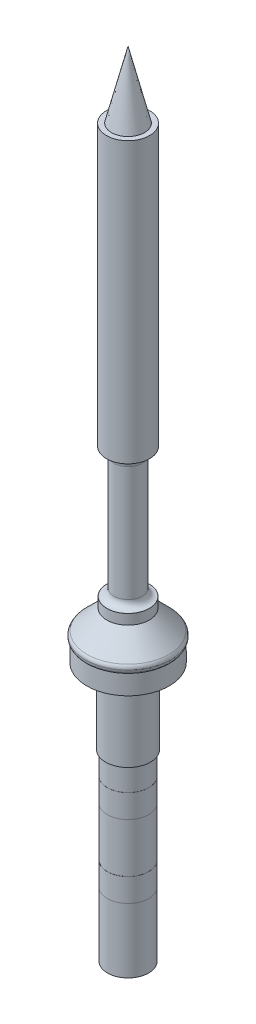
SolidWorks part; units mm, degrees
other "Ring 2"
other "Ring 1"
other "Core"
other "Tip"
ref_plane "Front Plane" through (0, 0, 0) normal (0, 0, 1) x (1, 0, 0)
ref_plane "Top Plane" through (0, 0, 0) normal (0, 1, 0) x (1, 0, 0)
ref_plane "Right Plane" through (0, 0, 0) normal (1, 0, 0) x (0, 0, -1)
sketch "Sketch1" plane through (0, 0, 0) normal (0, 1, 0) x (1, 0, 0)
  circle A0 centre (0, 0) radius 2.875
  dimension "D1" = 5.75
extrude "Boss-Extrude1" add sketch "Sketch1" along normal blind 9.7
sketch "Sketch2" plane through (0, 9.7, 0) normal (0, 1, 0) x (1, 0, 0)
  circle A0 centre (0, 0) radius 5.3
  dimension "D1" = 10.6
extrude "Boss-Extrude2" add sketch "Sketch2" along normal blind 2.5
sketch "Sketch3" plane through (0, 12.2, 0) normal (0, 1, 0) x (1, 0, 0)
  circle A0 centre (0, 0) radius 5.475
  dimension "D1" = 10.95
extrude "Boss-Extrude3" add sketch "Sketch3" along normal blind 0.8
sketch "Sketch4" plane through (0, 13, 0) normal (0, 1, 0) x (1, 0, 0)
  circle A1 centre (0, 0) radius 5.475
  circle A2 centre (0, 0) radius 5.475
  dimension "D1" = 0
extrude "Boss-Extrude4" add sketch "Sketch4" along normal blind 2.75 draft 45
sketch "Sketch5" plane through (0, 15.75, 0) normal (0, 1, 0) x (1, 0, 0)
  circle A1 centre (0, 0) radius 2.725
  circle A2 centre (0, 0) radius 2.725
  dimension "D1" = 0
extrude "Boss-Extrude5" add sketch "Sketch5" along normal blind 1.3
sketch "Sketch6" plane through (0, 17.05, 0) normal (0, 1, 0) x (1, 0, 0)
  circle A0 centre (0, 0) radius 1.805
  dimension "D1" = 3.61
extrude "Boss-Extrude6" add sketch "Sketch6" along normal blind 16.7
sketch "Sketch7" plane through (0, 33.75, 0) normal (0, 1, 0) x (1, 0, 0)
  circle A0 centre (0, 0) radius 2.775
  dimension "D1" = 5.55
extrude "Boss-Extrude7" add sketch "Sketch7" along normal blind 36
sketch "Sketch8" plane through (0, 69.75, 0) normal (0, 1, 0) x (1, 0, 0)
  circle A0 centre (0, 0) radius 2.125
  dimension "D1" = 4.25
extrude "Boss-Extrude8" add sketch "Sketch8" along normal blind 8.6 draft 13.9
sketch "Sketch9" plane through (0, 0, 0) normal (0, -1, 0) x (1, 0, 0)
  circle A0 centre (0, 0) radius 2.65
  dimension "D1" = 5.3
extrude "Boss-Extrude9" add sketch "Sketch9" along normal blind 23.6 separate body contours A0
ref_plane "Plane1" through (0, -2.95, 0) normal (0, -1, 0) x (-1, 0, 0)
sketch "Sketch10" plane through (0, -2.95, 0) normal (0, -1, 0) x (-1, 0, 0)
  circle A0 centre (0, 0) radius 2.66
  circle A1 centre (0, 0) radius 2.65
  circle A2 centre (0, 0) radius 2.65
  dimension "D1" = 0
  dimension "D2" = 0.01
extrude "Boss-Extrude10" add sketch "Sketch10" along normal blind 3 separate body
ref_plane "Plane2" through (0, -12.3, 0) normal (0, -1, 0) x (-1, 0, 0)
sketch "Sketch12" plane through (0, -12.3, 0) normal (0, -1, 0) x (-1, 0, 0)
  circle A0 centre (0, 0) radius 2.66
  circle A1 centre (0, 0) radius 2.65
  circle A2 centre (0, 0) radius 2.65
  dimension "D1" = 0
  dimension "D2" = 0.01
extrude "Boss-Extrude11" add sketch "Sketch12" along normal blind 3 separate body
fillet "Fillet1" radius 0.7 2 edges at (0, 12.2, 5.475) (0, 13, 5.475)
fillet "Fillet2" radius 0.9 1 edges at (0, 17.05, 1.805)
fillet "Fillet3" radius 1 1 edges at (0, 33.75, 1.805)
fillet "Fillet4" radius 0.3 1 edges at (0, 9.7, 2.875)
